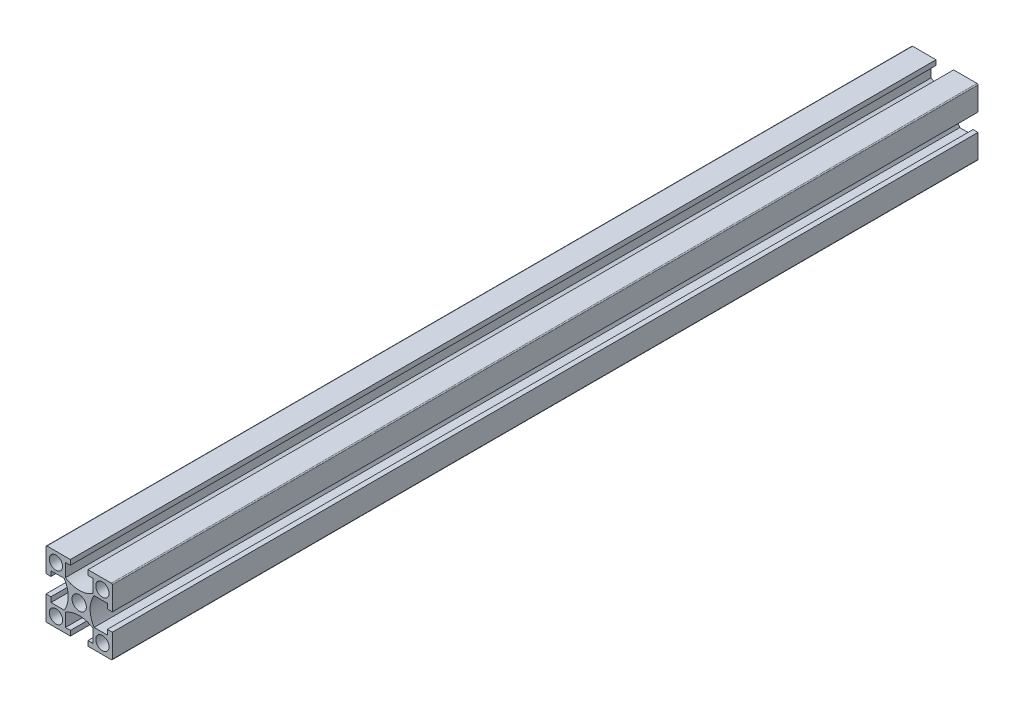
SolidWorks part; units mm, degrees
material "3.0255 (EN-AW 1350A)"
ref_plane "정면" through (0, 0, 0) normal (0, 0, 1) x (1, 0, 0)
ref_plane "윗면" through (0, 0, 0) normal (0, 1, 0) x (1, 0, 0)
ref_plane "우측면" through (0, 0, 0) normal (1, 0, 0) x (0, 0, -1)
sketch "스케치1" plane through (0, 0, 0) normal (0, 0, 1) x (1, 0, 0)
  line L0 (0, 32.0265) -> (0, -31.6588) construction
  line L1 (-10, 10) -> (-10, -10)
  line L2 (-10, 10) -> (10, 10)
  line L3 (-10, 2.65) -> (-8.5, 2.65)
  line L4 (13.6618, 0) -> (-11.6993, 0) construction
  line L5 (-8.5, 2.65) -> (-8.5, 4.15)
  line L6 (-8.5, 4.15) -> (-4.5032, 4.15)
  line L7 (-10, -2.65) -> (-8.5, -2.65)
  line L8 (-8.5, -2.65) -> (-8.5, -4.15)
  line L9 (-8.5, -4.15) -> (-4.5032, -4.15)
  line L10 (-10, -10) -> (10, -10)
  line L11 (10, 10) -> (10, -10)
  circle A0 centre (-7, 7) radius 2
  circle A1 centre (-7, -7) radius 2
  arc A2 (-4.5032, 4.15) -> (-4.5032, -4.15) centre (-11.0587, 0) cw
  circle A3 centre (0, 0) radius 2.15
  circle A4 centre (7, 7) radius 2
  circle A5 centre (7, -7) radius 2
  point P21 (-10, 0)
  point P23 (-3.3, 0)
  point P31 (0, -10)
  point P32 (0, 10)
  dimension "D3" = 4
  dimension "D9" = 6.7
  dimension "D10" = 4.3
  dimension "D11" = 7.7587
  dimension "D1" = 20
  dimension "D2" = 20
  dimension "D4" = 14
  dimension "D5" = 14
  dimension "D6" = 5.3
  dimension "D7" = 8.3
  dimension "D8" = 1.5
extrude "보스-돌출1" add sketch "스케치1" along normal blind 261 contours A0 | A4 | A3 | A5 | A1 | A2 L6 L5 L3 L1 L7 L8 L9 | L2 L11 L10 L1 region at (-6.6069, 0, 0) region at (-7, 7, 0) region at (-7, -7, 0) region at (0, 0, 0) region at (7, 7, 0) region at (7, -7, 0)
extrude "컷-돌출1" cut sketch "스케치1<3>" along normal up to next contours A2 L6 L5 L3 L1 L7 L8 L9 region at (-6.6069, 0, 0)
sketch "스케치1<3>" plane through (0, 0, 0) normal (0, 0, 1) x (1, 0, 0) same geometry as "스케치1"
pattern_circular "원형 패턴1" count 4 over 360 about axis through (0, 0, 261) along (0, 0, -1) of "컷-돌출1" reverse direction yes
fillet "필렛1" radius 0.3 4 edges at (10, -10, 130.5) (-10, -10, 130.5) (-10, 10, 130.5) (10, 10, 130.5)
sketch "스케치3" plane through (0, 10, 0) normal (0, 1, 0) x (1, 0, 0)
  circle A0 centre (0, -11) radius 2.5
  circle A1 centre (0, -250) radius 2.5
  dimension "D1" = 11
  dimension "D3" = 239
extrude "컷-돌출2" cut sketch "스케치3" against normal through all
sketch "스케치4" plane through (0, 10, 0) normal (0, 1, 0) x (1, 0, 0)
  circle A1 centre (0, -108) radius 2.15
  circle A2 centre (0, -160) radius 2.15
  circle A3 centre (0, -11) radius 2.5 construction
  dimension "D2" = 52
  dimension "D3" = 149
extrude "컷-돌출3" cut sketch "스케치4" against normal through all
